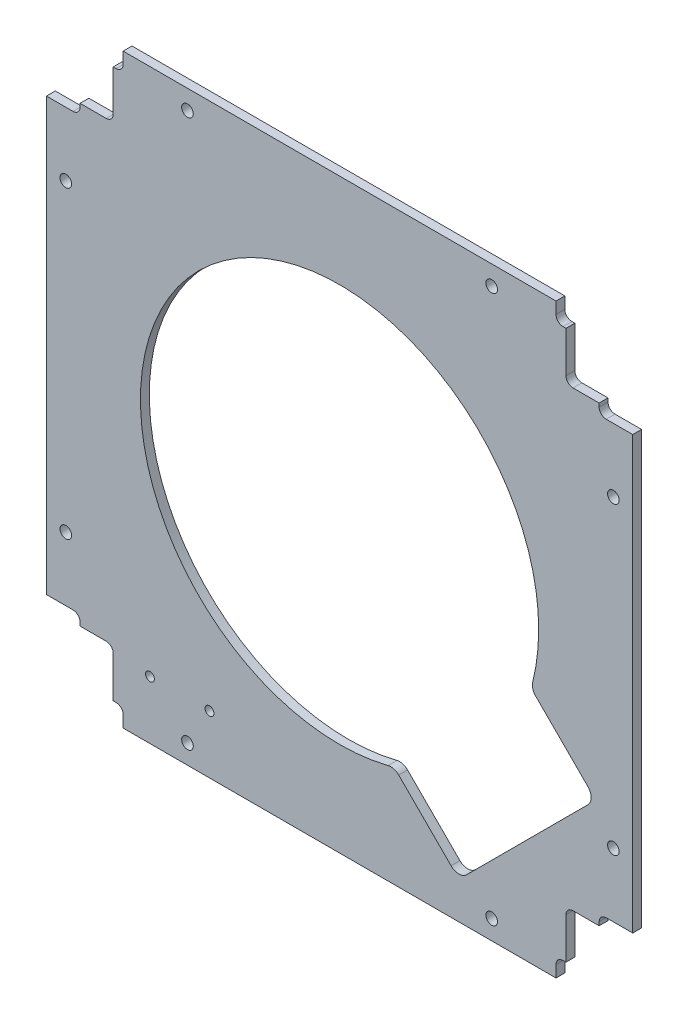
SolidWorks part; units mm, degrees
material "FR4_stuffedProtoboard"
ref_plane "Front Plane" through (0, 0, 0) normal (0, 0, 1) x (1, 0, 0)
ref_plane "Top Plane" through (0, 0, 0) normal (0, 1, 0) x (1, 0, 0)
ref_plane "Right Plane" through (0, 0, 0) normal (1, 0, 0) x (0, 0, -1)
sketch "Sketch1" plane through (0, 0, 0) normal (0, 0, 1) x (1, 0, 0)
  line L0 (53, 53) -> (-53, -53) construction
  line L1 (53, 53) -> (-53, 53)
  line L2 (53, 53) -> (53, -53)
  line L3 (53, -53) -> (-53, -53)
  line L4 (-53, 53) -> (-53, -53)
  point P4 (0, 0)
  dimension "D1" = 106
  dimension "D2" = 106
extrude "mainOutline" add sketch "Sketch1" along normal blind 1.6
sketch "axisLabels" plane through (0, 0, 0) normal (0, 0, -1) x (-1, 0, 0)
  text T0 "+Y"
  text T1 "+X"
sketch "Sketch4" plane through (0, 0, 0) normal (0, 0, -1) x (-1, 0, 0)
  line L10 (-53, 53) -> (53, 53) construction
  line L29 (41.3, 53) -> (41.3, 41.3)
  line L31 (53, 41.3) -> (41.3, 41.3)
  line L46 (53, 53) -> (53, -53) construction
  line L51 (53, 41.3) -> (53, 53)
  line L52 (53, 53) -> (41.3, 53)
  dimension "D11" = 11.7
  dimension "D12" = 11.7
extrude "railCutouts" cut sketch "Sketch4" against normal through all
sketch "Sketch13" plane through (0, 0, 0) normal (0, 0, -1) x (-1, 0, 0)
  line L0 (47.3, 39.4) -> (47.3, 41.3)
  line L2 (53, 41.3) -> (53, 39.4)
  line L5 (41.3, 53) -> (39.5, 53)
  line L6 (41.3, 53) -> (41.3, 50)
  line L7 (41.3, 50) -> (39.5, 50)
  line L8 (39.5, 53) -> (39.5, 50)
  line L9 (53, 41.3) -> (53, -53) construction
  line L10 (53, 41.3) -> (47.3, 41.3)
  line L12 (53, 39.4) -> (47.3, 39.4)
  line L13 (41.3, 41.3) -> (53, 41.3) construction
  dimension "D1" = 5.7
  dimension "D3" = 1.9
  dimension "D5" = 1.8
  dimension "D6" = 3
extrude "filletCutouts" cut sketch "Sketch13" against normal through all both and the other way through all
sketch "Sketch5" plane through (0, 0, 0) normal (0, 0, -1) x (-1, 0, 0)
  line L23 (42.198, 42.198) -> (45.4803, 45.4803) construction
  line L24 (41.3, 43.0961) -> (44.5823, 46.3784)
  line L25 (43.0961, 41.3) -> (46.3784, 44.5823)
  line L41 (41.3, 50) -> (41.3, 41.3) construction
  arc A14 (41.3, 43.0961) -> (43.0961, 41.3) centre (42.198, 42.198) ccw
  arc A15 (46.3784, 44.5823) -> (44.5823, 46.3784) centre (45.4803, 45.4803) ccw
  point P0 (41.3, 41.3)
  point P52 (43.8392, 43.8392)
  dimension "D14" = 1.27
  dimension "D7" = 45
extrude "dogbone" [suppressed] cut sketch "Sketch5" against normal through all
sketch "Sketch14" plane through (0, 0, 1.6) normal (0, 0, 1) x (1, 0, 0)
  point P1 (-47.3, 39.4)
sketch "Sketch27" plane through (0, 0, 1.6) normal (0, 0, 1) x (1, 0, 0)
  line L0 (-40.928, 42.198) -> (-40.928, 49.628)
  line L1 (-48.198, 39.028) -> (-53, 39.028)
  line L2 (-53, 39.4) -> (-53, -53) construction
  line L3 (-53, 39.028) -> (-53, 53)
  line L4 (-53, 53) -> (-39.128, 53)
  line L5 (-39.128, 53) -> (-39.128, 50.898)
  line L6 (-40.928, 49.628) -> (-40.398, 49.628)
  line L7 (-42.198, 40.928) -> (-46.928, 40.928)
  line L8 (-46.928, 40.928) -> (-46.928, 40.298)
  line L10 (53, 53) -> (-39.5, 53) construction
  arc A0 (-42.198, 40.928) -> (-40.928, 42.198) centre (-42.198, 42.198) ccw
  arc A1 (-40.398, 49.628) -> (-39.128, 50.898) centre (-40.398, 50.898) ccw
  arc A2 (-48.198, 39.028) -> (-46.928, 40.298) centre (-48.198, 40.298) ccw
  dimension "D1" = 1.27
extrude "smoothCorner" cut sketch "Sketch27" against normal blind 10
pattern_sketch "Sketch-Pattern1" [suppressed] of bodies 103 driven by "Sketch14"
mirror "Mirror1" about plane through (0, 0, 0) normal (1, 0, 0) of "smoothCorner", "filletCutouts", "railCutouts"
mirror "Mirror2" about plane through (0, 0, 0) normal (0, 1, 0) of "Mirror1"
fillet "Fillet1" [suppressed] radius 0.5
fillet "Fillet10" [suppressed] radius 0.5
hole_wizard "M2 Clearance Hole1" positions "Sketch8" profile "Sketch9" hole size "M2" standard "ANSI Metric" end condition through all
sketch "Sketch8" plane through (0, 0, 0) normal (0, 0, -1) x (-1, 0, 0)
  line L0 (53, 39.028) -> (53, -39.028) construction
  line L1 (39.128, -53) -> (-39.128, -53) construction
  line L2 (-53, -39.028) -> (-53, 39.028) construction
  line L3 (53, 0) -> (-53, 0) construction
  line L5 (0, -53) -> (0, -11.6379) construction
  line L6 (53, 39.028) -> (53, -39.028) construction
  point P0 (49.5, -27.5)
  point P1 (27.5, -49.5)
  point P5 (-49.5, -27.5)
  point P30 (-27.5, -49.5)
  point P31 (-27.5, 49.5)
  point P32 (-49.5, 27.5)
  point P33 (27.5, 49.5)
  point P34 (49.5, 27.5)
  dimension "D1" = 3.5
  dimension "D2" = 3.5
  dimension "D3" = 55
  dimension "D4" = 3.5
  dimension "D5" = 55
  dimension "D6" = 55
sketch "Sketch9" plane through (-49.5, -27.5, 0) normal (1, 0, 0) x (0, 1, 0)
  line L0 (0, 0) -> (0, 1.6)
  line L1 (0, 1.6) -> (1.05, 1.6)
  line L2 (1.05, 1.6) -> (1.05, 0)
  line L5 (1.05, 0) -> (0, 0)
  line L11 (0, -6.35) -> (0, 107.95) construction
  dimension "Thru Hole Dia." = 2.1
  dimension "Thru Hole Depth" = 1.6
sketch "Sketch15" plane through (0, 0, 0) normal (0, 0, -1) x (-1, 0, 0)
  line L0 (-39.128, 53) -> (39.128, 53) construction
  line L1 (45, 53) -> (-45, 53)
  line L2 (45, 53) -> (45, 46.8)
  line L3 (45, 46.8) -> (-45, 46.8)
  line L4 (-45, 53) -> (-45, 46.8)
  line L5 (45, -53) -> (-45, -53)
  line L6 (45, -53) -> (45, -46.8)
  line L7 (45, -46.8) -> (-45, -46.8)
  line L8 (-45, -53) -> (-45, -46.8)
  line L9 (39.128, -53) -> (-39.128, -53) construction
  line L10 (-53, -39.028) -> (-53, 39.028) construction
  line L11 (-53, 45) -> (-47.8, 45)
  line L12 (-53, 45) -> (-53, -45)
  line L13 (-53, -45) -> (-47.8, -45)
  line L14 (-47.8, 45) -> (-47.8, -45)
  line L15 (53, 45) -> (47.8, 45)
  line L16 (53, 45) -> (53, -45)
  line L17 (53, -45) -> (47.8, -45)
  line L18 (47.8, 45) -> (47.8, -45)
  line L19 (53, 39.028) -> (53, -39.028) construction
  point P8 (0, 53)
  point P11 (0, -53)
  point P22 (-53, 0)
  point P25 (53, 0)
  dimension "D1" = 90
  dimension "D3" = 6.2
  dimension "D5" = 5.2
extrude "Cut-Extrude5" cut sketch "Sketch15" against normal blind 0.001
sketch "Sketch11" plane through (0, 0, 0) normal (0, 0, -1) x (-1, 0, 0)
  circle A0 centre (0, 0) radius 36
  dimension "D1" = 72
extrude "Cut-Extrude2" cut sketch "Sketch11" against normal through all both and the other way through all
sketch "Sketch28" plane through (0, 0, 0) normal (0, 0, -1) x (-1, 0, 0)
  line L0 (-12.3744, 12.3744) -> (-46.3155, -21.5668)
  line L1 (-12.3744, 12.3744) -> (12.3744, -12.3744)
  line L2 (-46.3155, -21.5668) -> (-21.5668, -46.3155)
  line L3 (12.3744, -12.3744) -> (-21.5668, -46.3155)
  line L4 (-47.8, -39.092) -> (-47.8, 39.092) construction
  dimension "D1" = 35
  dimension "D2" = 48
  dimension "D3" = 315
extrude "Cut-Extrude7" cut sketch "Sketch28" against normal blind 10
fillet "Fillet11" radius 2 4 edges at (21.5668, -46.3155, 0.8) (9.8714, -34.6202, 0.8) (34.6202, -9.8714, 0.8) (46.3155, -21.5668, 0.8)
sketch "Sketch16" [suppressed] plane through (0, 0, 1.6) normal (0, 0, 1) x (1, 0, 0)
  line L4 (-45, -53) -> (45, -53)
  line L5 (45, -53) -> (45, -46.8)
  line L6 (45, -46.8) -> (-45, -46.8)
  line L7 (-45, -46.8) -> (-45, -53)
  line L8 (-45, -53) -> (45, -53)
  line L9 (45, -53) -> (45, -46.8)
  line L10 (45, -46.8) -> (-45, -46.8)
  line L11 (-45, -46.8) -> (-45, -53)
  line L12 (45, 53) -> (-45, 53)
  line L13 (45, 46.8) -> (45, 53)
  line L14 (-45, 46.8) -> (45, 46.8)
  line L15 (-45, 53) -> (-45, 46.8)
  line L16 (45, 53) -> (-45, 53)
  line L17 (45, 46.8) -> (45, 53)
  line L18 (-45, 46.8) -> (45, 46.8)
  line L19 (-45, 53) -> (-45, 46.8)
  line L20 (-47.8, 45) -> (-53, 45)
  line L21 (-53, 45) -> (-53, -45)
  line L22 (-53, -45) -> (-47.8, -45)
  line L23 (-47.8, -45) -> (-47.8, 45)
  line L24 (-47.8, 45) -> (-53, 45)
  line L25 (-53, 45) -> (-53, -45)
  line L26 (-53, -45) -> (-47.8, -45)
  line L27 (-47.8, -45) -> (-47.8, 45)
  line L28 (53, 45) -> (47.8, 45)
  line L29 (47.8, 45) -> (47.8, -45)
  line L30 (47.8, -45) -> (53, -45)
  line L31 (53, -45) -> (53, 45)
  line L32 (53, 45) -> (47.8, 45)
  line L33 (47.8, 45) -> (47.8, -45)
  line L34 (47.8, -45) -> (53, -45)
  line L35 (53, -45) -> (53, 45)
  dimension "D1" = 0
  dimension "D2" = 0
  dimension "D3" = 0
  dimension "D4" = 0
extrude "Cut-Extrude6" [suppressed] cut sketch "Sketch16" against normal blind 0.001
sketch "Sketch30" [suppressed] plane through (0, 0, 0) normal (0, 0, -1) x (-1, 0, 0)
  line L0 (-18.93, -39.33) -> (-2.75, -23.15)
  line L1 (-2.75, -23.15) -> (2.75, -23.15)
  line L2 (2.75, -23.15) -> (18.93, -39.33)
  line L3 (-39.33, -18.93) -> (-23.15, -2.75)
  line L4 (-23.15, -2.75) -> (-23.15, 2.75)
  line L5 (-23.15, 2.75) -> (-39.33, 18.93)
  line L6 (-18.93, 39.33) -> (-2.75, 23.15)
  line L7 (-2.75, 23.15) -> (2.75, 23.15)
  line L8 (2.75, 23.15) -> (18.93, 39.33)
  line L9 (39.33, -18.93) -> (23.15, -2.75)
  line L10 (23.15, -2.75) -> (23.15, 2.75)
  line L11 (23.15, 2.75) -> (39.33, 18.93)
  line L12 (0, -23.15) -> (0, 23.15) construction
  line L13 (-23.15, 0) -> (23.15, 0) construction
  arc A0 (-18.93, -39.33) -> (-39.33, -18.93) centre (-17.5661, -17.5661) cw
  arc A1 (-39.33, 18.93) -> (-18.93, 39.33) centre (-17.5661, 17.5661) cw
  arc A2 (18.93, 39.33) -> (39.33, 18.93) centre (17.5661, 17.5661) cw
  arc A3 (39.33, -18.93) -> (18.93, -39.33) centre (17.5661, -17.5661) cw
  dimension "D5" = 21.8066
  dimension "D1" = 135
  dimension "D2" = 28.85
  dimension "D3" = 22.882
  dimension "D4" = 5.5
extrude "Cut-Extrude8" [suppressed] cut sketch "Sketch30" against normal blind 10
sketch "Sketch29" plane through (0, 0, 0) normal (0, 0, -1) x (-1, 0, 0)
  circle A0 centre (34.285, -42.5) radius 0.8
  circle A1 centre (23.515, -42.5) radius 0.8
  circle A2 centre (49.5, -27.5) radius 1.05 construction
  circle A4 centre (27.5, -49.5) radius 1.05 construction
  dimension "D1" = 1.6
  dimension "D2" = 10.77
  dimension "D3" = 7
  dimension "D4" = 25.985
extrude "Connector Location" cut sketch "Sketch29" against normal blind 10
equation "\"ConnectorSideDistance\" = 25.985"
equation "\"ConnectorTopDistance\" = 7.0"
equation "\"D3@Sketch29\"=\"ConnectorTopDistance\""
equation "\"D4@Sketch29\"=\"ConnectorSideDistance\""
